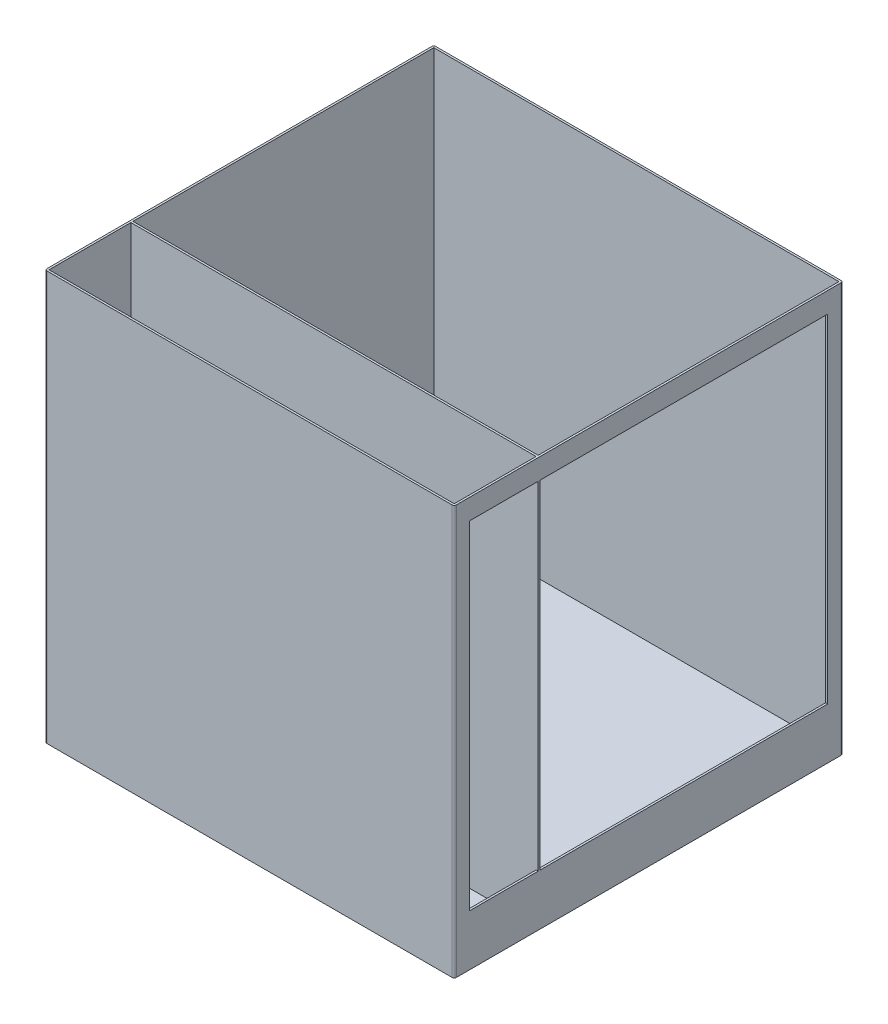
SolidWorks part; units mm, degrees
material "AISI 316 Stainless Steel Sheet (SS)"
ref_plane "Front" through (0, 0, 0) normal (0, 0, 1) x (1, 0, 0)
ref_plane "Top" through (0, 0, 0) normal (0, 1, 0) x (1, 0, 0)
ref_plane "Right" through (0, 0, 0) normal (1, 0, 0) x (0, 0, -1)
sketch "Sketch1" plane through (0, 0, 0) normal (0, 1, 0) x (1, 0, 0)
  line L1 (-200, -190) -> (200, -190)
  line L2 (-200, -190) -> (-200, 190)
  line L3 (-200, 190) -> (200, 190)
  line L4 (200, -190) -> (200, 190)
  line L5 (-200, -190) -> (200, 190) construction
  line L6 (-200, 190) -> (200, -190) construction
  point P0 (0, 0)
  dimension "D1" = 380
  dimension "D2" = 400
extrude "Boss-Extrude1" add sketch "Sketch1" along normal mid plane 400
fillet "Fillet1" radius 2 4 edges at (-200, 0, -190) (200, 0, -190) (200, 0, 190) (-200, 0, 190)
shell "Shell1" thickness 2 removed face at (0, 200, 0)
sketch "Sketch2" plane through (198, 0, 0) normal (-1, 0, 0) x (0, 0, 1)
  line L0 (0, -50) -> (0, 50) construction
  line L1 (-175, 180) -> (175, 180)
  line L2 (-175, 180) -> (-175, -150)
  line L3 (-175, -150) -> (175, -150)
  line L4 (175, 180) -> (175, -150)
  line L5 (-175, 180) -> (175, -150) construction
  line L6 (-175, -150) -> (175, 180) construction
  line L7 (188, 200) -> (-188, 200) construction
  line L8 (188, -200) -> (-188, -200) construction
  line L9 (190, -200) -> (190, 200) construction
  point P0 (0, 15)
  dimension "D1" = 20
  dimension "D2" = 50
  dimension "D3" = 350
  dimension "D4" = 15
extrude "Cut-Extrude1" cut sketch "Sketch2" against normal through all
sketch "Sketch3" plane through (0, 200, 0) normal (0, 1, 0) x (1, 0, 0)
  line L0 (-200, 188) -> (-200, -188) construction
  line L1 (-200, -106) -> (200, -106)
  line L2 (-200, -106) -> (-200, -108)
  line L3 (-200, -108) -> (200, -108)
  line L4 (200, -106) -> (200, -108)
  line L5 (200, -188) -> (200, 188) construction
  line L6 (-198, -188) -> (198, -188) construction
  dimension "D1" = 2
  dimension "D2" = 80
extrude "Boss-Extrude2" add sketch "Sketch3" against normal through all
